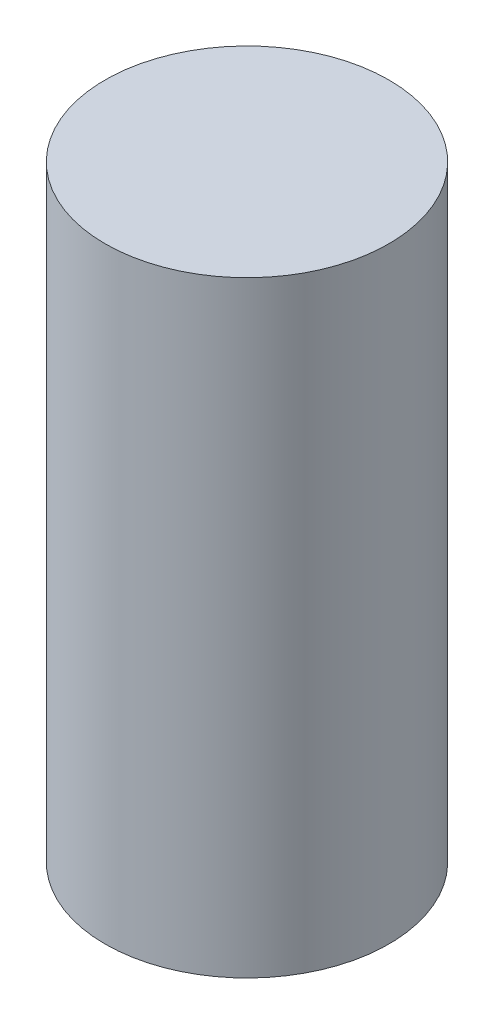
SolidWorks part; units mm, degrees
ref_plane "Front Plane" through (0, 0, 0) normal (0, 0, 1) x (1, 0, 0)
ref_plane "Top Plane" through (0, 0, 0) normal (0, 1, 0) x (1, 0, 0)
ref_plane "Right Plane" through (0, 0, 0) normal (1, 0, 0) x (0, 0, -1)
sketch "Sketch1" plane through (0, 0, 0) normal (0, 1, 0) x (1, 0, 0)
  circle A0 centre (0, 0) radius 3
  dimension "D1" = 6
extrude "Boss-Extrude1" add sketch "Sketch1" along normal blind 12.821
equation "\"bearing_21_OD\"= 21mm"
equation "\"pin_cirlce_diameter\"= 75mm"
equation "\"pin_diam\"= 6mm"
equation "\"gear_thickness\"= 4mm"
equation "\"ball_bearing_diam\"= 3.214mm"
equation "\"bearing_21_outer_clearance\"= 0.127mm'change this"
equation "\"bearing_15_OD\"= 15mm"
equation "\"bearing_15_outer_clearance\"= 0mm'change this"
equation "\"thrust_bearing_thickness\"= 5mm'measure this irl and change"
equation "\"D1@Boss-Extrude1\"=\"ball_bearing_diam\"*1.50+2*\"gear_thickness\""
